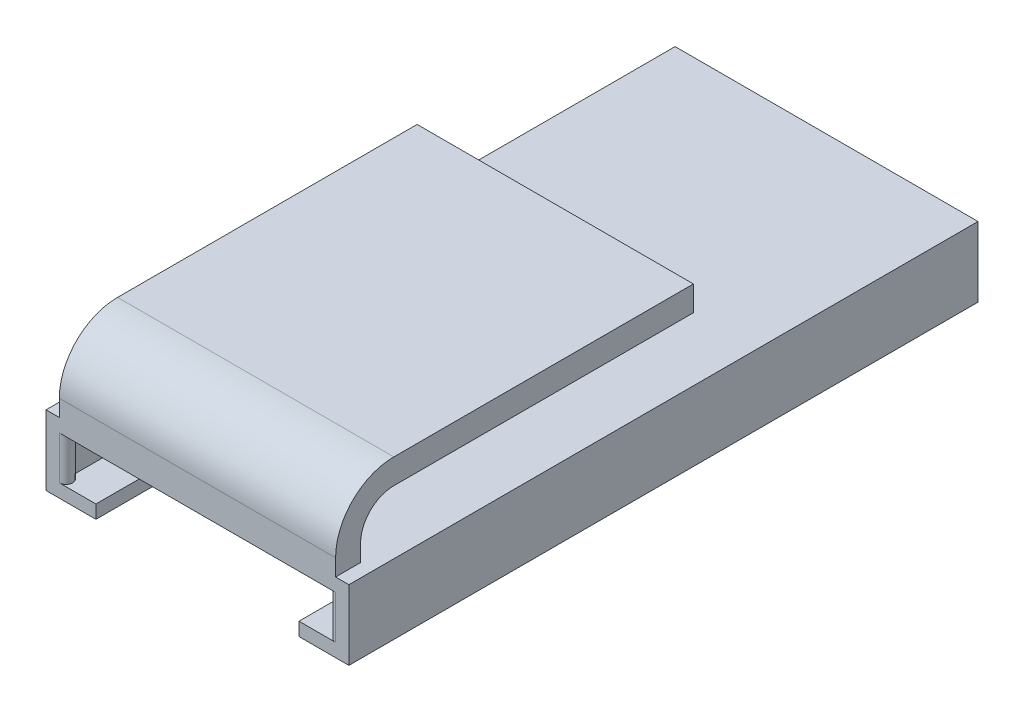
SolidWorks part; units mm, degrees
ref_plane "Front Plane" through (0, 0, 0) normal (0, 0, 1) x (1, 0, 0)
ref_plane "Top Plane" through (0, 0, 0) normal (0, 1, 0) x (1, 0, 0)
ref_plane "Right Plane" through (0, 0, 0) normal (1, 0, 0) x (0, 0, -1)
sketch "Sketch1" plane through (0, 0, 0) normal (0, 1, 0) x (1, 0, 0)
  line L0 (-1.6, -1.6) -> (-1.6, 74)
  line L1 (0, 0) -> (33.2, 0)
  line L2 (0, 0) -> (0, 72.4)
  line L3 (0, 72.4) -> (33.2, 72.4)
  line L4 (33.2, 0) -> (33.2, 72.4)
  line L5 (-1.6, 74) -> (34.8, 74)
  line L6 (34.8, -1.6) -> (34.8, 74)
  line L7 (-1.6, -1.6) -> (34.8, -1.6)
  dimension "D1" = 33.2
  dimension "D2" = 72.4
  dimension "D3" = 1.6
extrude "Boss-Extrude1" add sketch "Sketch1" along normal blind 5.2
sketch "Sketch2" plane through (0, 0, 0) normal (0, 1, 0) x (1, 0, 0)
  line L1 (-1.6, -1.6) -> (34.8, -1.6)
  line L2 (-1.6, -1.6) -> (-1.6, 74)
  line L3 (-1.6, 74) -> (34.8, 74)
  line L4 (34.8, -1.6) -> (34.8, 74)
extrude "Boss-Extrude2" add sketch "Sketch2" against normal blind 1.6
extrude "Boss-Extrude3" add sketch "Sketch2<2>" along normal blind 1.6 from offset 5.2
sketch "Sketch2<2>" plane through (0, 0, 0) normal (0, 1, 0) x (1, 0, 0) same geometry as "Sketch2"
sketch "Sketch3" plane through (0, 6.8, 0) normal (0, 1, 0) x (1, 0, 0)
  line L0 (0, 0) -> (33.2, 0)
  line L1 (0, -1.6) -> (33.2, -1.6)
  line L2 (-1.6, -1.6) -> (34.8, -1.6) construction
  arc A0 (33.2, 0) -> (33.2, -1.6) centre (33.2, -0.8) ccw
  arc A1 (0, 0) -> (0, -1.6) centre (0, -0.8) cw
  point P6 (0, 0)
  point P7 (0, 0)
  point P9 (0, -1.6)
  point P12 (0, 0)
  dimension "D1" = 1.6
  dimension "D2" = 1.6
extrude "Cut-Extrude1" cut sketch "Sketch3" against normal blind 5.2 from offset 1.6 offset against normal yes
sketch "Sketch4" plane through (34.8, 0, 0) normal (1, 0, 0) x (0, 0, -1)
  line L0 (1.4, 6.8) -> (1.4, 8.8)
  line L1 (-1.6, 6.8) -> (74, 6.8) construction
  line L2 (5.4, 12.8) -> (41.4, 12.8)
  line L3 (41.4, 12.8) -> (41.4, 15.8)
  line L4 (41.4, 15.8) -> (-1.6, 15.8)
  line L5 (-1.6, 15.8) -> (-1.6, 6.8)
  line L7 (1.4, 6.8) -> (-1.6, 6.8)
  arc A0 (1.4, 8.8) -> (5.4, 12.8) centre (5.4, 8.8) cw
  point P4 (0, 0)
  point P9 (0, 0)
  point P10 (0, 0)
  point P13 (1.4, 12.8)
  dimension "D6" = 4
  dimension "D1" = 6
  dimension "D2" = 3
  dimension "D3" = 3
  dimension "D4" = 1.6
  dimension "D5" = 40
extrude "Boss-Extrude4" add sketch "Sketch4" against normal blind 33.2 from offset 1.6 offset against normal yes
sketch "Sketch5" plane through (0, -1.6, 0) normal (0, -1, 0) x (1, 0, 0)
  line L0 (4.4, 1.6) -> (28.8, 1.6)
  line L1 (-1.6, 1.6) -> (34.8, 1.6) construction
  line L2 (28.8, 1.6) -> (28.8, -8.4)
  line L4 (4.4, -8.4) -> (4.4, 1.6)
  line L5 (-1.6, -74) -> (-1.6, 1.6) construction
  line L6 (34.8, 1.6) -> (34.8, -74) construction
  arc A0 (4.4, -8.4) -> (28.8, -8.4) centre (16.6, -8.4) ccw
  point P7 (0, 1.6)
  dimension "D1" = 6
  dimension "D2" = 6
  dimension "D3" = 10
extrude "Cut-Extrude2" cut sketch "Sketch5" against normal blind 2
fillet "Fillet1" radius 7 1 edges at (16.6, 15.8, 1.6)
equation "\"D2@Sketch3\"=\"D1@Sketch3\""
equation "\"D2@Sketch5\"=\"D1@Sketch5\""
